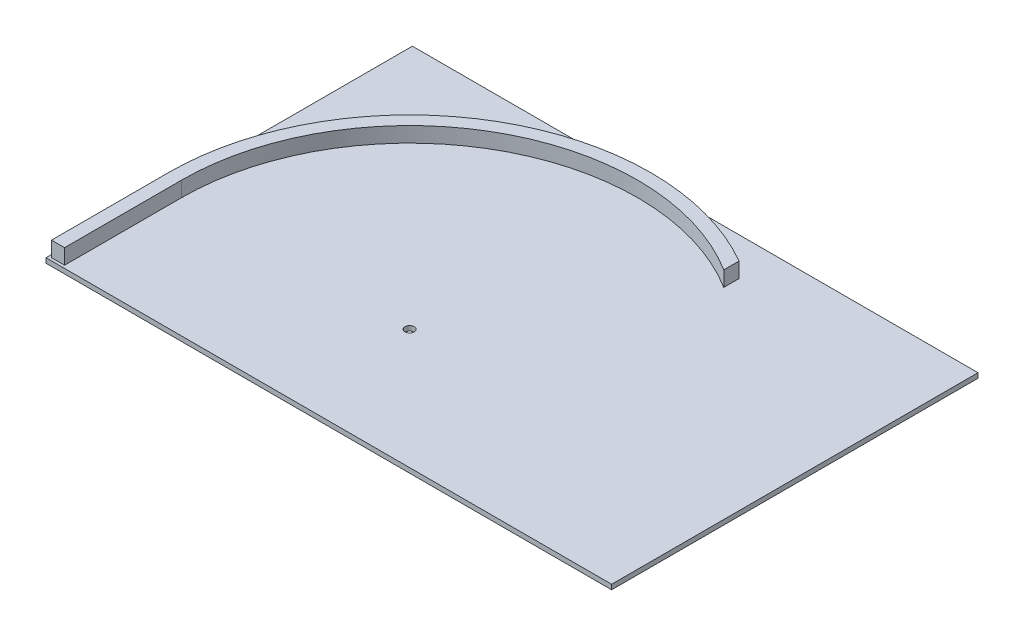
SolidWorks part; units mm, degrees
material "Particle Board"
ref_plane "Front Plane" through (0, 0, 0) normal (0, 0, 1) x (1, 0, 0)
ref_plane "Top Plane" through (0, 0, 0) normal (0, 1, 0) x (1, 0, 0)
ref_plane "Right Plane" through (0, 0, 0) normal (1, 0, 0) x (0, 0, -1)
sketch "Sketch3" plane through (0, 0, 0) normal (0, 1, 0) x (1, 0, 0)
  line L1 (0, 0) -> (-839.8654, 0) construction
  line L2 (0, 0) -> (-451.1992, 260.5) construction
  line L5 (-524, 0) -> (-554, 0)
  line L6 (277.6777, 444.3772) -> (277.6777, 479.3862)
  circle A0 centre (0, 0) radius 254 construction
  arc A3 (277.6777, 444.3772) -> (-524, 0) centre (0, 0) ccw
  arc A4 (277.6777, 479.3862) -> (-554, 0) centre (0, 0) ccw
  arc A5 (293.5753, 469.8186) -> (-554, 0) centre (0, 0) ccw construction
  dimension "D1" = 524
  dimension "D2" = 30
  dimension "D4" = 122
  dimension "D5" = 508
  dimension "D3" = 30
extrude "Boss-Extrude1" add sketch "Sketch3" along normal blind 35
sketch "Sketch4" plane through (0, 0, 0) normal (0, 1, 0) x (1, 0, 0)
  line L0 (-538.2597, 554) -> (609.3192, 554) construction
  line L5 (-560.35, 566.7) -> (739.65, 566.7)
  line L6 (-560.35, 566.7) -> (-560.35, -275.4)
  line L7 (-560.35, -275.4) -> (739.65, -275.4)
  line L8 (739.65, 566.7) -> (739.65, -275.4)
  arc A0 (277.6777, 479.3862) -> (-554, 0) centre (0, 0) ccw construction
  dimension "D1" = 275.4
  dimension "D2" = 6.35
  dimension "D3" = 12.7
  dimension "D4" = 1300
extrude "Boss-Extrude2" add sketch "Sketch4" against normal blind 11.1125
hole_wizard "Ø20.0mm Dowel Hole1" positions "Sketch6" profile "Sketch7" hole size "Ø20.0" standard "ANSI Metric" end condition through all
sketch "Sketch6" plane through (0, 0, 0) normal (0, 1, 0) x (1, 0, 0)
  point P0 (0, 0)
sketch "Sketch7" plane through (0, 0, 0) normal (1, 0, 0) x (0, 0, 1)
  line L0 (0, 0) -> (0, 11.1125)
  line L1 (0, 11.1125) -> (10.5, 11.1125)
  line L2 (10.5, 11.1125) -> (10.5, 0)
  line L5 (10.5, 0) -> (0, 0)
  line L11 (0, -6.35) -> (0, 107.95) construction
  dimension "Thru Hole Dia." = 21
  dimension "Thru Hole Depth" = 11.1125
ref_plane "Plane1" through (0, 0, 269.05) normal (0, 0, 1) x (1, 0, 0)
sketch "Sketch8" plane through (0, 0, 0) normal (0, 0, 1) x (1, 0, 0)
  line L1 (-554, 35) -> (-524, 35)
  line L2 (-554, 35) -> (-554, 0)
  line L3 (-554, 0) -> (-524, 0)
  line L4 (-524, 35) -> (-524, 0)
extrude "Boss-Extrude3" add sketch "Sketch8" along normal up to surface (269.05 mm away) up to plane "Plane1"
